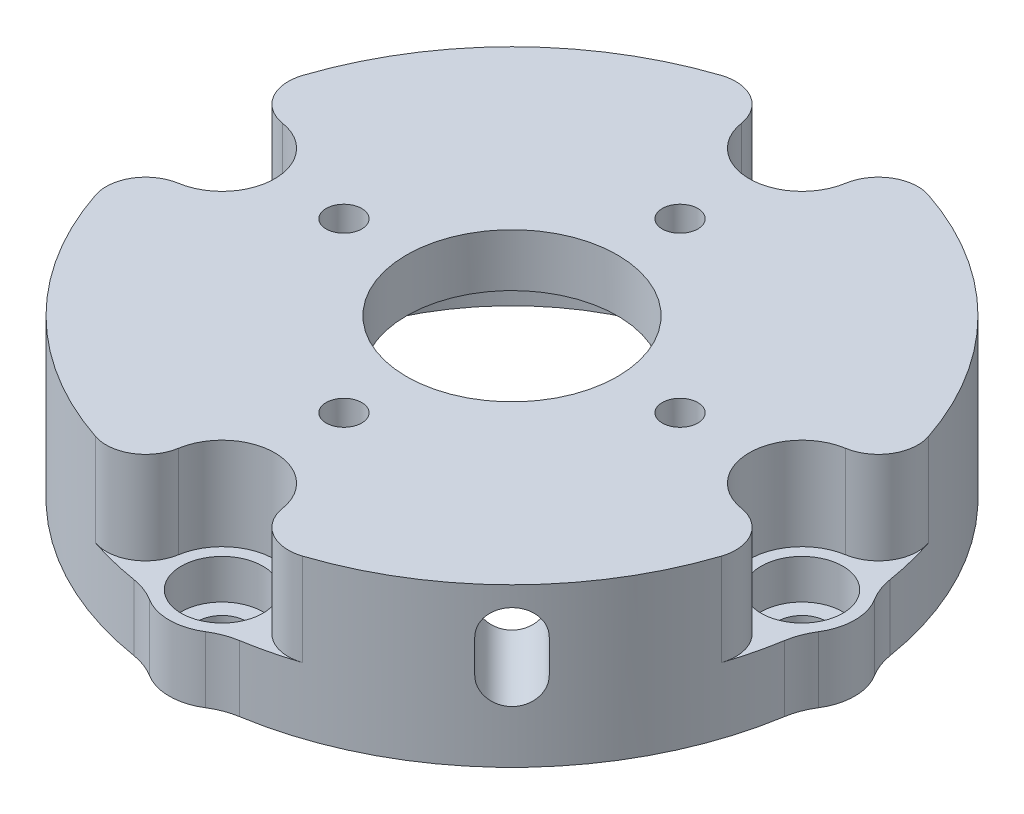
SolidWorks part; units mm, degrees
ref_plane "Front Plane" through (0, 0, 0) normal (0, 0, 1) x (1, 0, 0)
ref_plane "Top Plane" through (0, 0, 0) normal (0, 1, 0) x (1, 0, 0)
ref_plane "Right Plane" through (0, 0, 0) normal (1, 0, 0) x (0, 0, -1)
sketch "Sketch1" plane through (0, 0, 0) normal (0, 1, 0) x (1, 0, 0)
  circle A0 centre (0, 0) radius 25
  circle A1 centre (0, 0) radius 8
  dimension "D1" = 50
  dimension "D2" = 16
extrude "Boss-Extrude1" add sketch "Sketch1" against normal blind 4
sketch "Sketch2" plane through (0, -4, 0) normal (0, -1, 0) x (1, 0, 0)
  circle A0 centre (0, 0) radius 25
  circle A1 centre (0, 0) radius 25 construction
  circle A2 centre (0, 0) radius 17.9
  dimension "D1" = 35.8
extrude "Boss-Extrude4" add sketch "Sketch2" along normal blind 8
sketch "Sketch4" plane through (0, -12, 0) normal (0, -1, 0) x (1, 0, 0)
  circle A0 centre (0, 0) radius 22 construction
  circle A1 centre (0, 22) radius 3.1
  circle A2 centre (0, 22) radius 1.85
  circle A3 centre (0, 22) radius 4
  circle M7 centre (0, 0) radius 25
  dimension "D1" = 44
  dimension "D2" = 6.2
  dimension "D3" = 3.7
  dimension "D4" = 8
extrude "Boss-Extrude2" add sketch "Sketch4" against normal blind 5 contours A3 A1 M7 | A3 A1 M7 region at (2.5535, -12, 23.939) region at (0, -12, 25.383)
extrude "Boss-Extrude3" add sketch "Sketch4<5>" against normal blind 2 contours A2 A1 | A2 A1 region at (-3.0123, -12, 22)
sketch "Sketch4<5>" plane through (0, -12, 0) normal (0, -1, 0) x (1, 0, 0) same geometry as "Sketch4"
extrude "Cut-Extrude3" cut sketch "Sketch4<6>" against normal through all from surface contours A1 A2 M7 region at (-1.8221, -12, 19.6004) starting at face at (0, -10, 25.05)
sketch "Sketch4<6>" plane through (0, -12, 0) normal (0, -1, 0) x (1, 0, 0) same geometry as "Sketch4"
extrude "Cut-Extrude4" cut sketch "Sketch4<7>" against normal through all contours A2 | A2 region at (0, -12, 22)
sketch "Sketch4<7>" plane through (0, -12, 0) normal (0, -1, 0) x (1, 0, 0) same geometry as "Sketch4"
extrude "Cut-Extrude9" cut sketch "Sketch4<9>" against normal through all from surface contours A3 A1 M7 region at (2.5535, -12, 23.939) starting at face at (0, -7, 25.2416)
sketch "Sketch4<9>" plane through (0, -12, 0) normal (0, -1, 0) x (1, 0, 0) same geometry as "Sketch4"
sketch "Sketch5" plane through (0, 0, 0) normal (0, 1, 0) x (1, 0, 0)
  line L1 (2.4249, 12.75) -> (1.2124, 14.85)
  line L2 (1.2124, 14.85) -> (-1.2124, 14.85)
  line L3 (-1.2124, 14.85) -> (-2.4249, 12.75)
  line L4 (-2.4249, 12.75) -> (-1.2124, 10.65)
  line L5 (-1.2124, 10.65) -> (1.2124, 10.65)
  line L6 (1.2124, 10.65) -> (2.4249, 12.75)
  circle A0 centre (0, 0) radius 12.75 construction
  circle A1 centre (0, 12.75) radius 1.35
  circle A2 centre (0, 12.75) radius 2.1 construction
  dimension "D1" = 25.5
  dimension "D2" = 2.7
  dimension "D3" = 4.2
extrude "Cut-Extrude5" cut sketch "Sketch5" against normal up to next contours A1 region at (0, 0, -12.75)
extrude "Cut-Extrude7" cut sketch "Sketch5<4>" along normal blind 2 from surface starting at face at (0, -4, -11.4)
sketch "Sketch5<4>" plane through (0, 0, 0) normal (0, 1, 0) x (1, 0, 0) same geometry as "Sketch5"
fillet "Fillet5" radius 3 2 edges at (-2.8159, -3.5, 24.8409) (2.8159, -3.5, 24.8409)
fillet "Fillet4" radius 5 2 edges at (2.8159, -9.5, 24.8409) (-2.8159, -9.5, 24.8409)
pattern_circular "CirPattern1" count 4 over 360 about axis through (0, -4, 0) along (0, 1, 0) of "Boss-Extrude2", "Boss-Extrude3", "Cut-Extrude3", "Cut-Extrude4", "Cut-Extrude9", "Cut-Extrude5", "Cut-Extrude7", "Fillet5", "Fillet4" reverse direction yes
ref_plane "Plane2" through (6.375, 0, 6.375) normal (0.7071, 0, 0.7071) x (0.7071, 0, -0.7071)
sketch "Sketch7" plane through (6.375, 0, 6.375) normal (0.7071, 0, 0.7071) x (0.7071, 0, -0.7071)
  line L0 (0, -6) -> (0, -3.5) construction
  line L1 (0, -12) -> (0, -7) construction
  line L2 (-2, -6) -> (-2, -3.5)
  line L3 (2, -6) -> (2, -3.5)
  line L4 (27.5, 0) -> (-27.5, 0) construction
  arc A0 (-2, -6) -> (2, -6) centre (0, -6) ccw
  arc A1 (2, -3.5) -> (-2, -3.5) centre (0, -3.5) ccw
  point P5 (0, -4.75)
  dimension "D1" = 2
  dimension "D3" = 2.5
  dimension "D2" = 3.5
extrude "Cut-Extrude8" cut sketch "Sketch7" along normal up to next and the other way up to next
equation "\"D2@Sketch7\"=\"D1@Sketch7\"+1.5"
